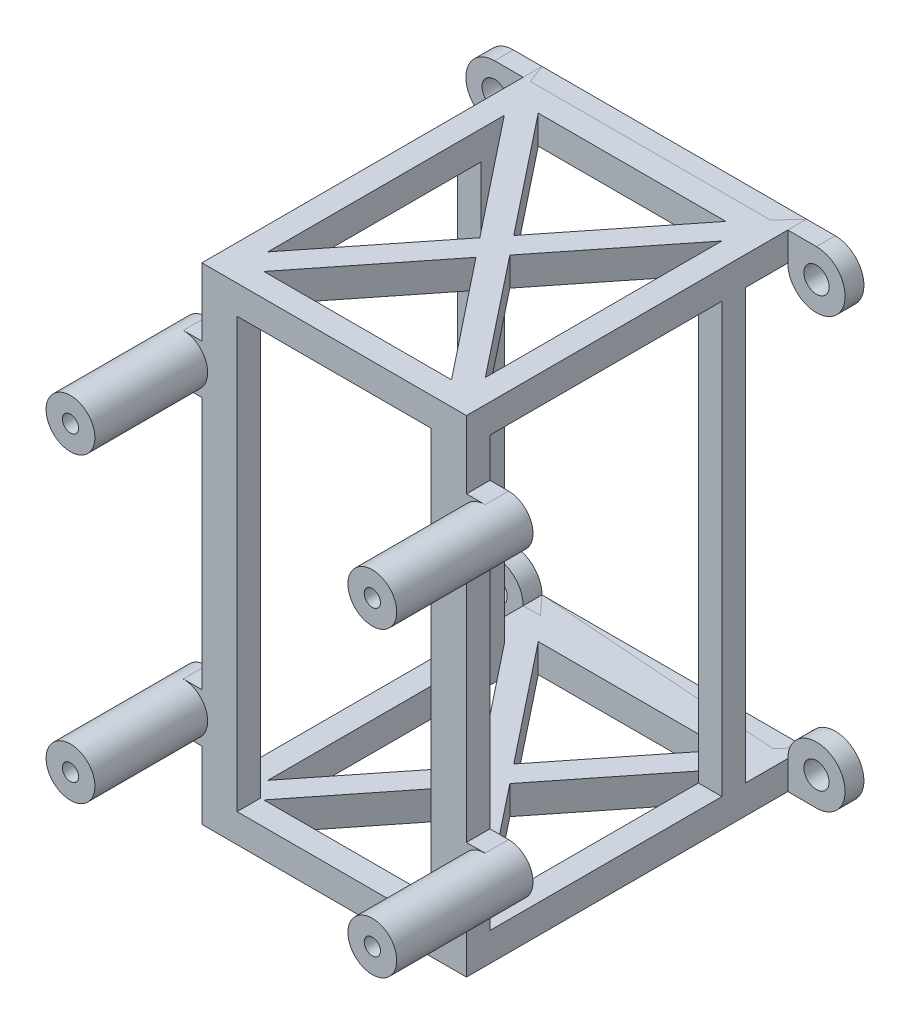
SolidWorks part; units mm, degrees
material "ABS PC"
ref_plane "Front Plane" through (0, 0, 0) normal (0, 0, 1) x (1, 0, 0)
ref_plane "Top Plane" through (0, 0, 0) normal (0, 1, 0) x (1, 0, 0)
ref_plane "Right Plane" through (0, 0, 0) normal (1, 0, 0) x (0, 0, -1)
sketch "Sketch1" plane through (0, 0, 0) normal (0, 0, 1) x (1, 0, 0)
  line L0 (-21.7551, 32.8676) -> (21.7551, 32.8676)
  line L1 (-21.7551, -28.9941) -> (21.7551, -28.9941) construction
  line L2 (-21.7551, -28.9941) -> (-21.7551, 28.9941) construction
  line L3 (-21.7551, 28.9941) -> (21.7551, 28.9941) construction
  line L4 (21.7551, -28.9941) -> (21.7551, 28.9941) construction
  line L5 (-21.7551, -28.9941) -> (21.7551, 28.9941) construction
  line L6 (-21.7551, 28.9941) -> (21.7551, -28.9941) construction
  line L7 (-21.7551, -32.8676) -> (21.7551, -32.8676)
  line L8 (-17.8816, 28.9941) -> (17.8816, 28.9941)
  line L9 (-17.8816, -28.9941) -> (17.8816, -28.9941)
  line L15 (-19.4303, -25.8958) -> (19.4303, 25.8958) construction
  line L16 (-19.4303, 25.8958) -> (19.4303, -25.8958) construction
  circle A0 centre (-21.7551, 28.9941) radius 3.8735
  circle A1 centre (21.7551, 28.9941) radius 3.8735
  circle A2 centre (21.7551, 28.9941) radius 1.7018
  circle A3 centre (-21.7551, 28.9941) radius 1.7018
  circle A4 centre (-21.7551, -28.9941) radius 3.8735
  circle A5 centre (-21.7551, -28.9941) radius 1.7018
  circle A6 centre (21.7551, -28.9941) radius 1.7018
  circle A7 centre (21.7551, -28.9941) radius 3.8735
  point P0 (0, 0)
  point P22 (0, 0)
  dimension "D3" = 7.747
  dimension "D4" = 3.4036
  dimension "D1" = 43.5102
  dimension "D2" = 57.9882
extrude "Boss-Extrude2" add sketch "Sketch1" along normal blind 2.54 contours A4 A0 | A0 A3 | A1 L0 A0 | A1 A2 | A7 A1 | A7 A6 | A7 A4 L7 | A4 A5 region at (0, 30.9784, 0) region at (-19.0936, 31.6556, 0) region at (24.4166, 31.6556, 0) region at (0, -30.9784, 0) region at (-24.4166, -26.3326, 0) region at (19.0936, -31.6556, 0)
sketch "Sketch2" plane through (0, 0, 2.54) normal (0, 0, 1) x (1, 0, 0)
  line L4 (-17.8816, 28.9941) -> (17.8816, 28.9941)
  line L9 (-17.8816, -28.9941) -> (17.8816, -28.9941)
  line L10 (17.8816, -28.9941) -> (17.8816, -32.8676)
  line L11 (17.8816, 28.9941) -> (17.8816, 32.8676)
  line L12 (-21.7551, 32.8676) -> (21.7551, 32.8676) construction
  line L13 (17.8816, 32.8676) -> (-17.8816, 32.8676)
  line L14 (-17.8816, 32.8676) -> (-17.8816, 28.9941)
  line L15 (-21.7551, -32.8676) -> (21.7551, -32.8676) construction
  line L16 (17.8816, -32.8676) -> (-17.8816, -32.8676)
  line L17 (-17.8816, -32.8676) -> (-17.8816, -28.9941)
  point P4 (0, 0)
extrude "Boss-Extrude3" add sketch "Sketch2" along normal blind 45.974 from surface separate body starting at face at (0, -28.593, 0)
sketch "Sketch6" plane through (0, 32.8676, 0) normal (0, 1, 0) x (1, 0, 0)
  line L0 (-17.8816, -2.54) -> (17.8816, -2.54)
  line L1 (-21.7551, -2.54) -> (21.7551, -2.54) construction
  line L2 (-12.6804, -42.799) -> (14.7066, -8.2696)
  line L3 (-14.7066, -42.799) -> (14.7066, -42.799)
  line L4 (17.8816, 0) -> (-17.8816, 0)
  line L5 (-17.8816, 0) -> (-17.8816, -45.974)
  line L6 (-17.8816, -45.974) -> (17.8816, -45.974)
  line L7 (17.8816, -45.974) -> (17.8816, 0)
  line L9 (-17.8816, -2.54) -> (-17.8816, -45.974)
  line L10 (-17.8816, -45.974) -> (17.8816, -45.974)
  line L11 (17.8816, -45.974) -> (17.8816, -2.54)
  line L12 (-14.7066, -42.799) -> (-14.7066, -5.715)
  line L13 (-14.7066, -5.715) -> (14.7066, -5.715)
  line L14 (14.7066, -42.799) -> (14.7066, -5.715)
  line L15 (-14.7066, -42.799) -> (14.7066, -5.715) construction
  line L16 (-14.7066, -5.715) -> (14.7066, -42.799) construction
  line L17 (12.6804, -5.715) -> (-14.7066, -40.2444)
  line L18 (12.6804, -42.799) -> (-14.7066, -8.2696)
  line L19 (-12.6804, -5.715) -> (14.7066, -40.2444)
  point P8 (0, -24.257)
  dimension "D2" = 3.175
  dimension "D3" = 3.175
  dimension "D4" = 3.175
  dimension "D5" = 3.175
  dimension "D6" = 1.5875
  dimension "D7" = 1.5875
  dimension "D8" = 1.5875
  dimension "D9" = 1.5875
  dimension "D1" = 0
extrude "Cut-Extrude3" cut sketch "Sketch6" against normal through all contours L17 L18 L12 | L13 L19 L17 | L2 L19 L14 | L3 L18 L2 region at (0, 32.8676, 37.4699) region at (10.4798, 32.8676, 24.257) region at (-10.4798, 32.8676, 24.257) region at (0, 32.8676, 11.0441)
sketch "Sketch7" plane through (0, 0, 0) normal (0, 0, 1) x (1, 0, 0)
  line L0 (-13.1191, -17.1002) -> (-13.1191, 17.1002)
  line L1 (-20.4, -20.4) -> (20.4, -20.4) construction
  line L2 (-20.4, -20.4) -> (-20.4, 20.4) construction
  line L3 (-20.4, 20.4) -> (20.4, 20.4) construction
  line L4 (20.4, -20.4) -> (20.4, 20.4) construction
  line L5 (-20.4, -20.4) -> (20.4, 20.4) construction
  line L6 (-20.4, 20.4) -> (20.4, -20.4) construction
  line L7 (-17.8816, 32.8676) -> (-17.8816, 23.6999)
  line L8 (-20.4, 23.6999) -> (-17.8816, 23.6999)
  line L9 (-13.1191, 32.8676) -> (-13.1191, 17.1002)
  line L10 (-20.4, 17.1002) -> (-17.8816, 17.1002)
  line L11 (13.1191, 32.8676) -> (13.1191, 17.1002)
  line L12 (17.8816, 17.1002) -> (20.4, 17.1002)
  line L13 (20.4, 23.6999) -> (17.8816, 23.6999)
  line L14 (17.8816, 32.8676) -> (17.8816, 23.6999)
  line L15 (-13.1191, -32.8676) -> (-13.1191, -17.1002)
  line L16 (-20.4, -17.1002) -> (-17.8816, -17.1002)
  line L17 (-20.4, -23.6999) -> (-17.8816, -23.6999)
  line L18 (-17.8816, -23.6999) -> (-17.8816, -32.8676)
  line L19 (-17.8816, -32.8676) -> (-13.1191, -32.8676)
  line L20 (-17.8816, 32.8676) -> (-13.1191, 32.8676)
  line L21 (13.1191, 32.8676) -> (17.8816, 32.8676)
  line L22 (20.4, -17.1002) -> (17.8816, -17.1002)
  line L23 (13.1191, -17.1002) -> (13.1191, -32.8676)
  line L24 (-17.8816, -32.8676) -> (17.8816, -32.8676) construction
  line L25 (13.1191, -32.8676) -> (17.8816, -32.8676)
  line L26 (17.8816, -32.8676) -> (17.8816, -23.6999)
  line L27 (17.8816, -23.6999) -> (20.4, -23.6999)
  line L28 (-17.8816, 17.1002) -> (-17.8816, -17.1002)
  line L29 (13.1191, 17.1002) -> (13.1191, -17.1002)
  line L30 (17.8816, 17.1002) -> (17.8816, -17.1002)
  circle A0 centre (20.4, 20.4) radius 3.2998
  circle A1 centre (-20.4, 20.4) radius 3.2998
  circle A2 centre (-20.4, -20.4) radius 3.2998
  circle A3 centre (20.4, -20.4) radius 3.2998
  circle A4 centre (-20.4, 20.4) radius 1.0999
  circle A5 centre (20.4, 20.4) radius 1.0999
  circle A6 centre (-20.4, -20.4) radius 1.0999
  circle A7 centre (20.4, -20.4) radius 1.0999
  point P0 (0, 0)
  dimension "D3" = 6.5997
  dimension "D8" = 2.1999
  dimension "D1" = 40.8
  dimension "D2" = 40.8
  dimension "D4" = 4.7625
  dimension "D5" = 4.7625
  dimension "D6" = 4.7625
  dimension "D7" = 4.7625
extrude "Boss-Extrude4" add sketch "Sketch7" against normal blind 3.175 from surface contours A1 L10 L9 L20 L7 L8 | A1 | A0 | A0 L13 L14 L21 L11 L12 | A3 L22 L23 L25 L26 L27 | A3 | A2 | A2 L17 L18 L19 L15 L16 region at (-15.5046, 0, 0) region at (-23.6065, -20.4, 0) region at (-18.1327, 22.6674, 0) region at (15.5046, 0, 0) region at (22.6674, 22.6674, 0) region at (17.1935, -20.4, 0) starting at face at (0, 30.9308, 45.974)
sketch "Sketch8" plane through (0, 0, 45.974) normal (0, 0, 1) x (1, 0, 0)
  circle A0 centre (-20.4, 20.4) radius 3.2998
  circle A1 centre (-20.4, 20.4) radius 1.0999
  circle A2 centre (20.4, 20.4) radius 1.0999
  circle A3 centre (20.4, 20.4) radius 3.2998
  circle A4 centre (20.4, -20.4) radius 1.0999
  circle A5 centre (20.4, -20.4) radius 3.2998
  circle A6 centre (-20.4, -20.4) radius 1.0999
  circle A7 centre (-20.4, -20.4) radius 3.2998
extrude "Boss-Extrude5" add sketch "Sketch8" along normal blind 15.24
sketch "Sketch9" plane through (0, 32.8676, 0) normal (0, 1, 0) x (1, 0, 0)
  line L0 (-14.7066, -8.2696) -> (-17.8816, -8.2696)
  line L1 (-17.8816, -45.974) -> (-17.8816, 0) construction
  line L2 (-17.8816, -8.2696) -> (-17.8816, -11.4446)
  line L3 (-17.8816, -11.4446) -> (-14.7066, -11.4446)
  line L4 (-14.7066, -40.2444) -> (-14.7066, -8.2696) construction
  line L5 (-14.7066, -11.4446) -> (-14.7066, -8.2696)
  line L6 (14.7066, -8.2696) -> (17.8816, -8.2696)
  line L7 (17.8816, -45.974) -> (17.8816, 0) construction
  line L8 (17.8816, -8.2696) -> (17.8816, -11.4446)
  line L9 (17.8816, -11.4446) -> (14.7066, -11.4446)
  line L10 (14.7066, -40.2444) -> (14.7066, -8.2696) construction
  line L11 (14.7066, -11.4446) -> (14.7066, -8.2696)
  dimension "D1" = 3.175
  dimension "D2" = 3.175
extrude "Boss-Extrude6" add sketch "Sketch9" against normal up to surface (57.9882 mm away) from surface up to face at (-10.4798, -28.9941, 24.257) starting at face at (0, 28.9941, 11.0441)
